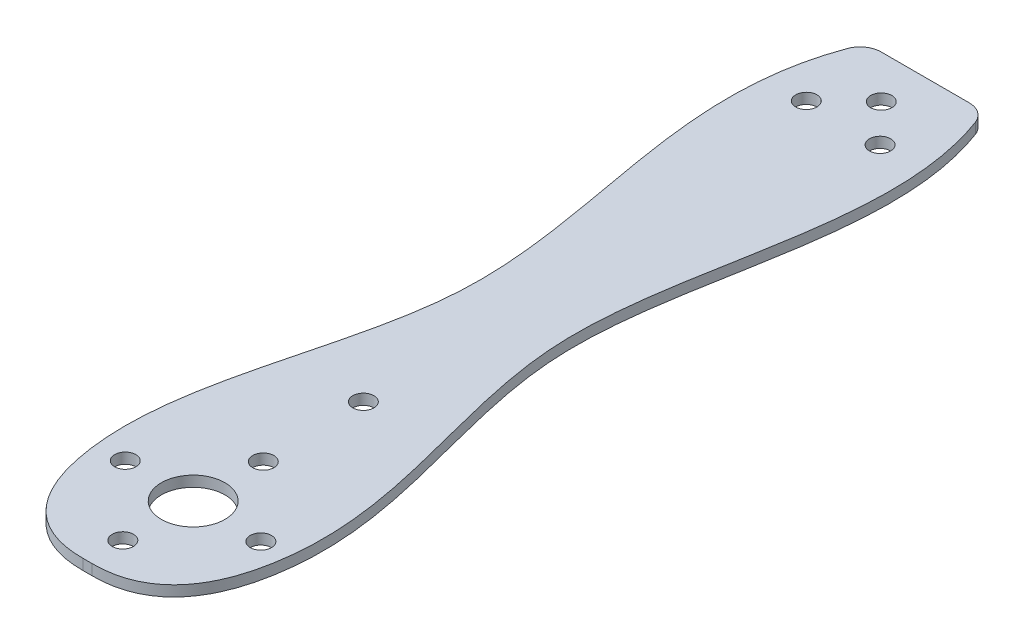
SolidWorks part; units mm, degrees
ref_plane "Front Plane" through (0, 0, 0) normal (0, 0, 1) x (1, 0, 0)
ref_plane "Top Plane" through (0, 0, 0) normal (0, 1, 0) x (1, 0, 0)
ref_plane "Right Plane" through (0, 0, 0) normal (1, 0, 0) x (0, 0, -1)
sketch "Sketch1" plane through (0, 0, 0) normal (0, 1, 0) x (1, 0, 0)
  line L2 (5.2752, 88.9) -> (-5.2747, 88.9)
  arc A0 (-0.5524, -11.4436) -> (0.5462, -11.4451) centre (-0.1058, -87.6423) cw
  arc A1 (7.6564, 87.2441) -> (5.2752, 88.9) centre (5.2752, 86.36) ccw
  arc A2 (-5.2747, 88.9) -> (-7.6561, 87.2435) centre (-5.2747, 86.36) ccw
  spline S0 degree 3 poles (-0.5524, -11.4436) (-4.8921, -11.469) (-9.5294, -8.0668) (-14.6459, 10.818) (0.653, 38.8317) (-11.939, 68.4666) (-8.6939, 84.4462) (-7.6561, 87.2435) knots 0.003862 0.003862 0.003862 0.003862 0.096354 0.162149 0.527592 0.902665 0.983926 0.983926 0.983926 0.983926
  spline S1 degree 3 poles (0.5462, -11.4451) (4.7056, -11.4807) (9.4269, -8.1856) (14.7819, 10.7254) (-0.6874, 38.8281) (11.9385, 68.4664) (8.695, 84.4468) (7.6564, 87.2441) knots 0.003868 0.003868 0.003868 0.003868 0.093614 0.162314 0.527685 0.902684 0.983934 0.983934 0.983934 0.983934
  dimension "D1" = 2.54
extrude "Boss-Extrude2" add sketch "Sketch1" along normal blind 1.27
sketch "Sketch2" plane through (0, 1.27, 0) normal (0, 1, 0) x (1, 0, 0)
  circle A0 centre (0, 21.59) radius 1.27
extrude "Cut-Extrude1" cut sketch "Sketch2" against normal through all
sketch3d "3DSketch1"
  circle A0 centre (0.2113, 3.81, -9.3896) radius 1.27 construction
  circle A1 centre (-8.1504, 3.81, -1.2161) radius 1.27 construction
  circle A2 centre (0.1037, 3.81, -1.0967) radius 3.81 construction
  circle A3 centre (8.3574, 3.81, -0.9527) radius 1.27 construction
  circle A4 centre (-0.0286, 3.81, 7.1959) radius 1.27 construction
  circle A5 centre (0.2113, 3.81, -9.3896) radius 1.27
  circle A6 centre (-8.1504, 3.81, -1.2161) radius 1.27
  circle A7 centre (0.1037, 3.81, -1.0967) radius 3.81
  circle A8 centre (8.3574, 3.81, -0.9527) radius 1.27
  circle A9 centre (-0.0286, 3.81, 7.1959) radius 1.27
  point P2 (0.2113, 5.08, -9.3896)
  point P5 (-8.1504, 5.08, -1.2161)
  point P8 (0.1037, 7.62, -1.0967)
  point P11 (8.3574, 5.08, -0.9527)
  point P14 (-0.0286, 5.08, 7.1959)
  point P16 (0.2113, 5.08, -9.3896)
  point P18 (-8.1504, 5.08, -1.2161)
  point P20 (0.1037, 7.62, -1.0967)
  point P22 (8.3574, 5.08, -0.9527)
  point P24 (-0.0286, 5.08, 7.1959)
extrude "Cut-Extrude8" cut sketch "3DSketch1" along direction (0, 1, 0) on the side against the normal through all
sketch "Sketch4" plane through (0, 1.27, 0) normal (0, 1, 0) x (1, 0, 0)
  circle A0 centre (-4.6847, 79.3365) radius 1.27 construction
  circle A1 centre (-0.1235, 83.7544) radius 1.27 construction
  circle A2 centre (4.2944, 79.1933) radius 1.27 construction
  circle A3 centre (-4.6847, 79.3365) radius 1.27
  circle A4 centre (-0.1235, 83.7544) radius 1.27
  circle A5 centre (4.2944, 79.1933) radius 1.27
extrude "Cut-Extrude9" cut sketch "Sketch4" against normal through all
